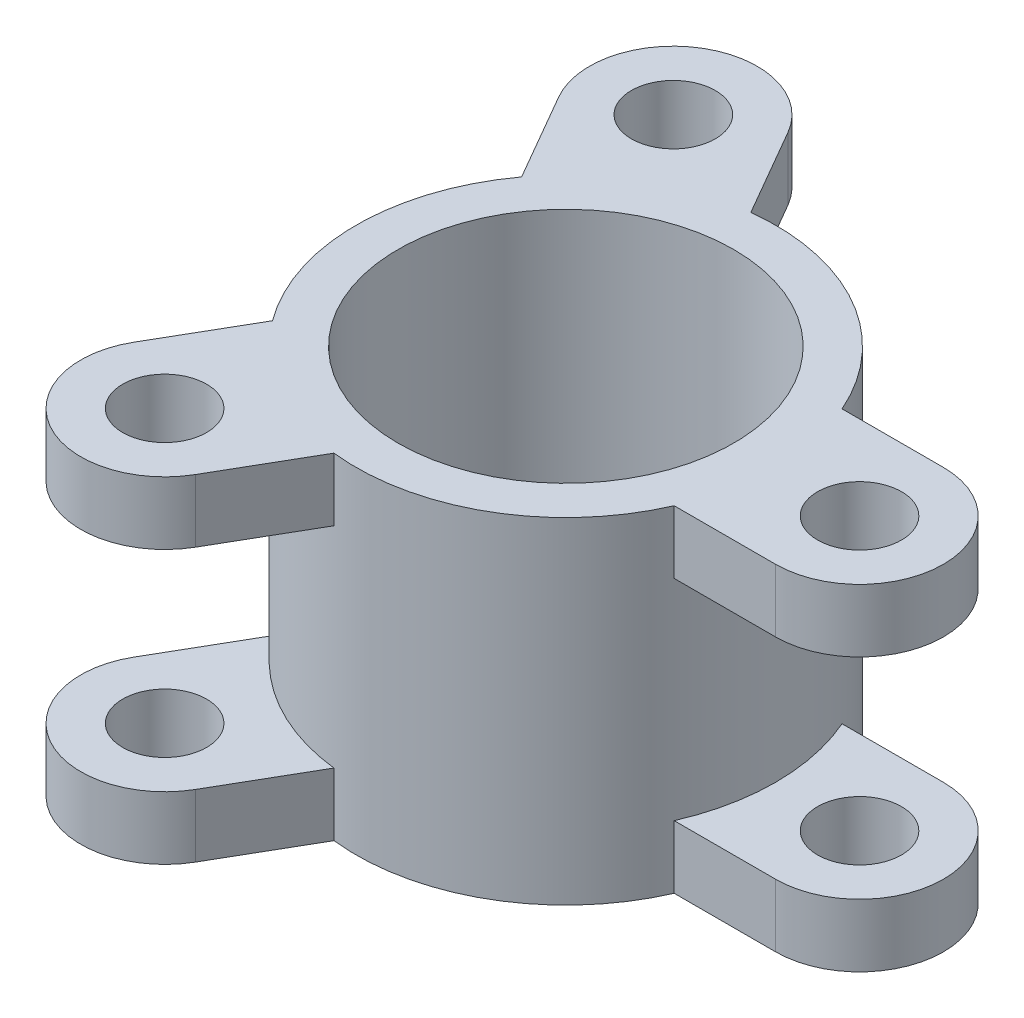
SolidWorks part; units mm, degrees
ref_plane "Front Plane" through (0, 0, 0) normal (0, 0, 1) x (1, 0, 0)
ref_plane "Top Plane" through (0, 0, 0) normal (0, 1, 0) x (1, 0, 0)
ref_plane "Right Plane" through (0, 0, 0) normal (1, 0, 0) x (0, 0, -1)
sketch "Sketch1" plane through (0, 0, 0) normal (0, 1, 0) x (1, 0, 0)
  line L0 (-88.163, 0) -> (88.163, 0) construction
  line L1 (0, 77.7113) -> (0, -77.7113) construction
  line L2 (70, 32.9806) -> (70, -32.9806) construction
  line L3 (70, 20) -> (45.8258, 20)
  line L4 (70, -20) -> (45.8258, -20)
  line L5 (-17.6795, -70.6218) -> (-5.5924, -49.6863)
  line L6 (-52.3205, -50.6218) -> (-40.2334, -29.6863)
  line L7 (-6.438, -77.1121) -> (-63.562, -44.1315) construction
  line L8 (-52.3205, 50.6218) -> (-40.2334, 29.6863)
  line L9 (-17.6795, 70.6218) -> (-5.5924, 49.6863)
  line L10 (-63.562, 44.1315) -> (-6.438, 77.1121) construction
  circle A0 centre (0, 0) radius 40
  circle A1 centre (0, 0) radius 50
  circle A2 centre (0, 0) radius 70 construction
  circle A3 centre (70, 0) radius 10
  arc A4 (70, 20) -> (70, -20) centre (70, 0) cw
  arc A5 (-17.6795, -70.6218) -> (-52.3205, -50.6218) centre (-35, -60.6218) cw
  circle A6 centre (-35, -60.6218) radius 10
  arc A7 (-52.3205, 50.6218) -> (-17.6795, 70.6218) centre (-35, 60.6218) cw
  circle A8 centre (-35, 60.6218) radius 10
  point P8 (0, 0)
  point P11 (0, 0)
  point P16 (70, 0)
  point P39 (0, 0)
  dimension "D1" = 80
  dimension "D2" = 100
  dimension "D3" = 140
  dimension "D4" = 20
  dimension "D5" = 20
  dimension "D6" = 3
extrude "Boss-Extrude2" add sketch "Sketch1" along normal blind 80 contours A1 A0 region at (47.5609, 0, -9.9265)
extrude "Boss-Extrude4" add sketch "Sketch1<4>" along normal blind 15 contours A5 L5 A1 L6 A6 | A7 L8 A1 L9 A8 | A4 L3 A1 L4 A3 region at (89.4041, 0, 0) region at (-25.3548, 0, -43.9158) region at (-12.2505, 0, 59.7992)
sketch "Sketch1<4>" plane through (0, 0, 0) normal (0, 1, 0) x (1, 0, 0) same geometry as "Sketch1"
ref_plane "Plane1" through (0, 40, 0) normal (0, 1, 0) x (1, 0, 0)
mirror "Mirror1" about plane through (0, 40, 0) normal (0, 1, 0) of "Boss-Extrude4"
